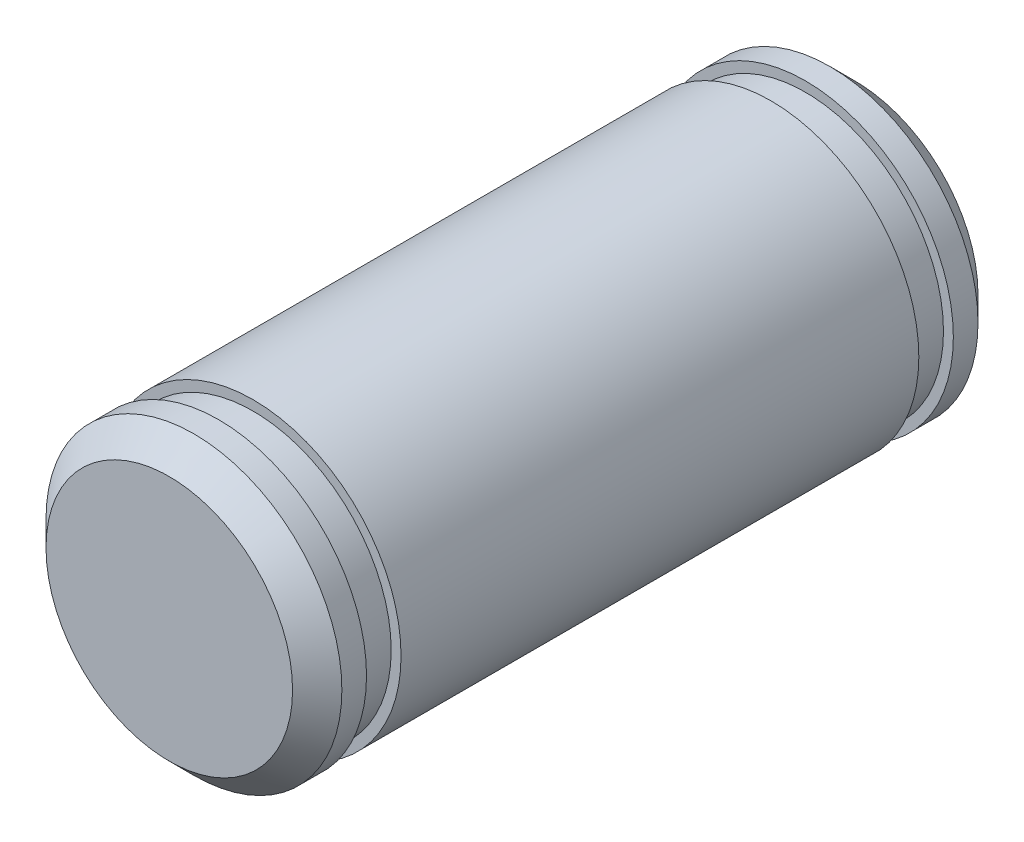
SolidWorks part; units mm, degrees
material "Chromowa stal nierdzewna"
ref_plane "Płaszczyzna przednia" through (0, 0, 0) normal (0, 0, 1) x (1, 0, 0)
ref_plane "Płaszczyzna górna" through (0, 0, 0) normal (0, 1, 0) x (1, 0, 0)
ref_plane "Płaszczyzna prawa" through (0, 0, 0) normal (1, 0, 0) x (0, 0, -1)
sketch "Szkic1" plane through (0, 0, 0) normal (0, 0, 1) x (1, 0, 0)
  circle A0 centre (0, 0) radius 3
  dimension "D1" = 6
extrude "Dodanie-wyciągnięcie1" add sketch "Szkic1" along normal blind 13.9
chamfer "Sfazowanie1" distance 0.5 angle 45 2 edges at (3, 0, 0) (3, 0, 13.9)
sketch "Szkic2" plane through (0, 0, 13.9) normal (0, 0, 1) x (1, 0, 0)
  circle A0 centre (0, 0) radius 3
  circle A1 centre (0, 0) radius 2.8
  dimension "D1" = 6
  dimension "D2" = 5.6
extrude "Wytnij-wyciągnięcie1" cut sketch "Szkic2" against normal blind 0.7 from offset 1 offset against normal yes
sketch "Szkic3" plane through (0, 0, 0) normal (0, 0, -1) x (-1, 0, 0)
  circle A0 centre (0, 0) radius 3
  circle A1 centre (0, 0) radius 2.8
  dimension "D1" = 5.6
  dimension "D2" = 6
extrude "Wytnij-wyciągnięcie2" cut sketch "Szkic3" against normal blind 0.7 from offset 1 offset against normal yes
